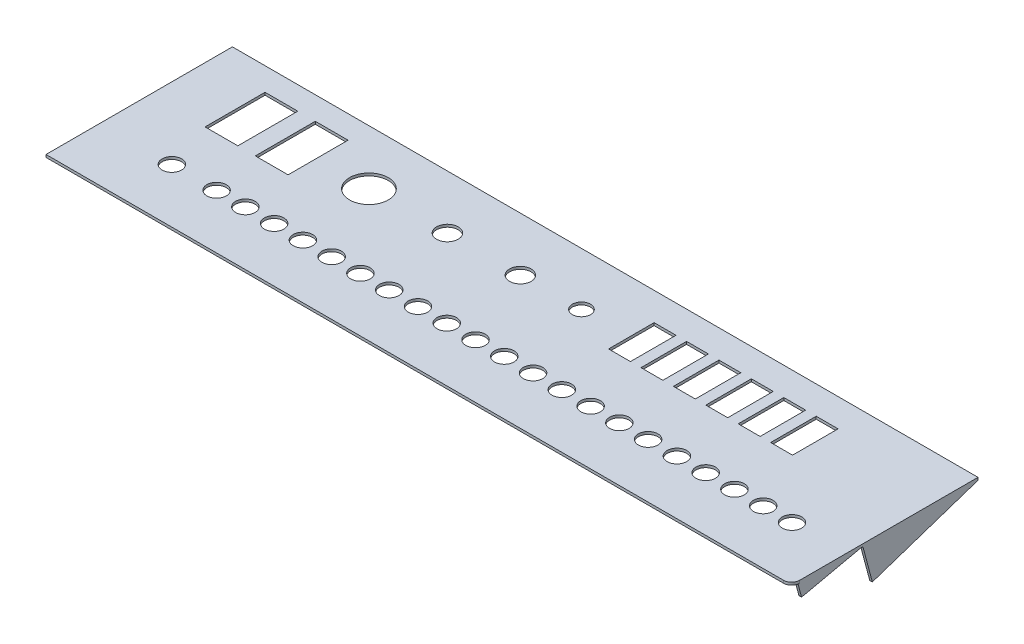
SolidWorks part; units mm, degrees
ref_plane "Front Plane" through (0, 0, 0) normal (0, 0, 1) x (1, 0, 0)
ref_plane "Top Plane" through (0, 0, 0) normal (0, 1, 0) x (1, 0, 0)
ref_plane "Right Plane" through (0, 0, 0) normal (1, 0, 0) x (0, 0, -1)
sketch "Boceto" plane through (0, 0, 0) normal (0, 1, 0) x (1, 0, 0)
  line L0 (-59.1, 30.6902) -> (-173.0029, 30.6902) construction
  line L5 (-59.1, -51.6098) -> (395.9, -51.6098) construction
  line L6 (-59.1, -51.6098) -> (-59.1, 63.3902) construction
  line L7 (-59.1, 63.3902) -> (395.9, 63.3902) construction
  line L8 (395.9, -51.6098) -> (395.9, 63.3902) construction
  line L9 (-28.6, 48.9902) -> (-8.6, 48.9902) construction
  line L10 (-28.6, 48.9902) -> (-28.6, 12.3902) construction
  line L11 (-28.6, 12.3902) -> (-8.6, 12.3902) construction
  line L12 (-8.6, 48.9902) -> (-8.6, 12.3902) construction
  line L13 (-28.6, 48.9902) -> (-8.6, 12.3902) construction
  line L14 (-28.6, 12.3902) -> (-8.6, 48.9902) construction
  line L15 (-59.1, -18.1098) -> (395.9, -18.1098) construction
  line L16 (2.4, 12.3902) -> (22.4, 12.3902) construction
  line L17 (2.4, 12.3902) -> (2.4, 48.9902) construction
  line L18 (2.4, 48.9902) -> (22.4, 48.9902) construction
  line L19 (22.4, 12.3902) -> (22.4, 48.9902) construction
  line L20 (2.4, 12.3902) -> (22.4, 48.9902) construction
  line L21 (2.4, 48.9902) -> (22.4, 12.3902) construction
  line L22 (174.9, 49.7902) -> (194.9, 49.7902) construction
  line L23 (174.9, 49.7902) -> (174.9, 11.7902) construction
  line L24 (174.9, 11.7902) -> (194.9, 11.7902) construction
  line L25 (194.9, 49.7902) -> (194.9, 11.7902) construction
  line L26 (174.9, 49.7902) -> (194.9, 11.7902) construction
  line L27 (174.9, 11.7902) -> (194.9, 49.7902) construction
  line L34 (211.4, 17.5561) -> (331, 17.5561) construction
  line L35 (211.4, 17.5561) -> (211.4, 46.5902) construction
  line L36 (211.4, 46.5902) -> (331, 46.5902) construction
  line L37 (331, 17.5561) -> (331, 46.5902) construction
  line L38 (211.4, 17.5561) -> (331, 46.5902) construction
  line L39 (211.4, 46.5902) -> (331, 17.5561) construction
  circle A0 centre (54.9, 29.6902) radius 11.1 construction
  circle A1 centre (102.75, 30.2402) radius 4.85 construction
  circle A2 centre (147.75, 30.2402) radius 4.85 construction
  circle A3 centre (-18.9, -18.1098) radius 6 construction
  circle A4 centre (8.7, -18.1098) radius 6 construction
  circle A5 centre (26.45, -18.1098) radius 6 construction
  circle A6 centre (44.2, -18.1098) radius 6 construction
  circle A7 centre (61.95, -18.1098) radius 6 construction
  circle A8 centre (79.7, -18.1098) radius 6 construction
  circle A9 centre (97.45, -18.1098) radius 6 construction
  circle A10 centre (115.2, -18.1098) radius 6 construction
  circle A11 centre (132.95, -18.1098) radius 6 construction
  circle A12 centre (150.7, -18.1098) radius 6 construction
  circle A13 centre (168.45, -18.1098) radius 6 construction
  circle A14 centre (186.2, -18.1098) radius 6 construction
  circle A15 centre (203.95, -18.1098) radius 6 construction
  circle A16 centre (221.7, -18.1098) radius 6 construction
  circle A17 centre (239.45, -18.1098) radius 6 construction
  circle A18 centre (257.2, -18.1098) radius 6 construction
  circle A19 centre (274.95, -18.1098) radius 6 construction
  circle A20 centre (292.7, -18.1098) radius 6 construction
  circle A21 centre (310.45, -18.1098) radius 6 construction
  circle A22 centre (328.2, -18.1098) radius 6 construction
  circle A23 centre (345.95, -18.1098) radius 6 construction
  circle A24 centre (363.7, -18.1098) radius 6 construction
  point P0 (0, 0)
  point P6 (-18.6, 30.6902)
  point P13 (12.4, 30.6902)
  point P24 (184.9, 30.7902)
  point P34 (271.2, 32.0731)
  dimension "D10" = 22.2
  dimension "D11" = 33.7
  dimension "D14" = 9.7
  dimension "D17" = 9.7
  dimension "D23" = 12
  dimension "D29" = 81.5
  dimension "D30" = 12
  dimension "D1" = 455
  dimension "D2" = 115
  dimension "D3" = 14.4
  dimension "D4" = 30.5
  dimension "D5" = 20
  dimension "D6" = 36.6
  dimension "D7" = 11
  dimension "D8" = 20
  dimension "D9" = 36.6
  dimension "D12" = 114
  dimension "D13" = 161.85
  dimension "D15" = 33.15
  dimension "D16" = 33.15
  dimension "D18" = 206.85
  dimension "D19" = 20
  dimension "D20" = 38
  dimension "D21" = 13.6
  dimension "D22" = 234
  dimension "D24" = 270.5
  dimension "D25" = 119.6
  dimension "D26" = 16.8
  dimension "D27" = 29.0341
  dimension "D28" = 40.2
  dimension "D31" = 27.6
  dimension "D32" = 21
sketch "Sketch4" plane through (0, 0, 0) normal (0, 1, 0) x (1, 0, 0)
  line L0 (-28.6, 48.9902) -> (-8.6, 12.3902) construction
  line L1 (-60.5474, 63.3902) -> (394.4526, 63.3902)
  line L3 (-60.5474, -51.6098) -> (391.9526, -51.6098)
  line L5 (-28.7093, 12.1902) -> (-8.4907, 12.1902)
  line L6 (-28.7093, 12.1902) -> (-28.7093, 49.1902)
  line L7 (-28.7093, 49.1902) -> (-8.4907, 49.1902)
  line L8 (-8.4907, 12.1902) -> (-8.4907, 49.1902)
  line L9 (-28.7093, 12.1902) -> (-8.4907, 49.1902) construction
  line L10 (-28.7093, 49.1902) -> (-8.4907, 12.1902) construction
  line L11 (-28.6, 12.3902) -> (-8.6, 48.9902) construction
  line L12 (2.4, 12.3902) -> (22.4, 48.9902) construction
  line L17 (2.2907, 12.1902) -> (2.2907, 49.1902)
  line L18 (2.2907, 12.1902) -> (22.5093, 12.1902)
  line L19 (22.5093, 12.1902) -> (22.5093, 49.1902)
  line L20 (2.2907, 49.1902) -> (22.5093, 49.1902)
  line L21 (102.75, 30.2402) -> (199.8359, 30.2402) construction
  line L22 (211.4, 32.0731) -> (331, 32.0731) construction
  line L23 (211.4, 17.5561) -> (211.4, 46.5902) construction
  line L24 (331, 17.5561) -> (331, 46.5902) construction
  line L25 (247.9, 46.1231) -> (247.9, 18.0231)
  line L26 (227.9, 46.1231) -> (214.4, 46.1231)
  line L27 (227.9, 46.1231) -> (227.9, 18.0231)
  line L28 (227.9, 18.0231) -> (214.4, 18.0231)
  line L29 (214.4, 46.1231) -> (214.4, 18.0231)
  line L30 (227.9, 46.1231) -> (214.4, 18.0231) construction
  line L31 (227.9, 18.0231) -> (214.4, 46.1231) construction
  line L32 (247.9, 46.1231) -> (234.4, 46.1231)
  line L33 (234.4, 46.1231) -> (234.4, 18.0231)
  line L34 (247.9, 18.0231) -> (234.4, 18.0231)
  line L35 (267.9, 46.1231) -> (267.9, 18.0231)
  line L36 (267.9, 46.1231) -> (254.4, 46.1231)
  line L37 (254.4, 46.1231) -> (254.4, 18.0231)
  line L38 (267.9, 18.0231) -> (254.4, 18.0231)
  line L39 (287.9, 46.1231) -> (287.9, 18.0231)
  line L40 (287.9, 46.1231) -> (274.4, 46.1231)
  line L41 (274.4, 46.1231) -> (274.4, 18.0231)
  line L42 (287.9, 18.0231) -> (274.4, 18.0231)
  line L43 (307.9, 46.1231) -> (307.9, 18.0231)
  line L44 (307.9, 46.1231) -> (294.4, 46.1231)
  line L45 (294.4, 46.1231) -> (294.4, 18.0231)
  line L46 (307.9, 18.0231) -> (294.4, 18.0231)
  line L47 (327.9, 46.1231) -> (327.9, 18.0231)
  line L48 (327.9, 46.1231) -> (314.4, 46.1231)
  line L49 (314.4, 46.1231) -> (314.4, 18.0231)
  line L50 (327.9, 18.0231) -> (314.4, 18.0231)
  line L52 (-60.5474, 63.3902) -> (-63.0474, 63.3902)
  line L54 (-60.5474, -51.6098) -> (-63.0474, -51.6098)
  line L55 (-63.0474, 63.3902) -> (-63.0474, -51.6098)
  line L58 (394.4526, 63.3902) -> (396.9526, 63.3902)
  line L59 (396.9526, -46.6098) -> (396.9526, 63.3902)
  circle A0 centre (54.9, 29.6902) radius 11.95
  circle A1 centre (102.75, 30.2402) radius 6.65
  circle A4 centre (147.75, 30.2402) radius 6.65
  circle A6 centre (184.9, 30.7902) radius 5.6
  circle A7 centre (-18.9, -18.1098) radius 6
  circle A8 centre (8.7, -18.1098) radius 6
  circle A9 centre (26.45, -18.1098) radius 6
  circle A10 centre (44.2, -18.1098) radius 6
  circle A11 centre (61.95, -18.1098) radius 6
  circle A12 centre (79.7, -18.1098) radius 6
  circle A13 centre (97.45, -18.1098) radius 6
  circle A14 centre (115.2, -18.1098) radius 6
  circle A15 centre (132.95, -18.1098) radius 6
  circle A16 centre (150.7, -18.1098) radius 6
  circle A17 centre (168.45, -18.1098) radius 6
  circle A18 centre (186.2, -18.1098) radius 6
  circle A19 centre (203.95, -18.1098) radius 6
  circle A20 centre (221.7, -18.1098) radius 6
  circle A21 centre (239.45, -18.1098) radius 6
  circle A22 centre (257.2, -18.1098) radius 6
  circle A23 centre (274.95, -18.1098) radius 6
  circle A24 centre (292.7, -18.1098) radius 6
  circle A25 centre (310.45, -18.1098) radius 6
  circle A26 centre (328.2, -18.1098) radius 6
  circle A27 centre (345.95, -18.1098) radius 6
  circle A28 centre (363.7, -18.1098) radius 6
  arc A29 (396.9526, -46.6098) -> (391.9526, -51.6098) centre (391.9526, -46.6098) cw
  point P6 (-18.6, 30.6902)
  point P15 (12.4, 30.6902)
  point P40 (221.15, 32.0731)
  dimension "D3" = 23.9
  dimension "D4" = 13.3
  dimension "D5" = 2
  dimension "D6" = 11.2
  dimension "D11" = 12
  dimension "D13" = 5
  dimension "D1" = 37
  dimension "D2" = 2
  dimension "D7" = 13.5
  dimension "D8" = 28.1
  dimension "D9" = 3
  dimension "D14" = 2.5
  dimension "D15" = 2.5
  dimension "D10" = 6
  dimension "D12" = 21
extrude "Boss-Extrude1" add sketch "Sketch4" along normal blind 1.6
sketch "Sketch5" plane through (396.9526, 0, 0) normal (1, 0, 0) x (0, 0, -1)
  line L0 (63.3902, 0) -> (-7.6098, 0)
  line L1 (-46.6098, 0) -> (63.3902, 0) construction
  line L2 (-7.6098, 0) -> (-1.7864, -21.7333)
  line L3 (-1.7864, -21.7333) -> (63.3902, 0)
  line L4 (-9.1098, 0) -> (-47.6098, 0)
  line L5 (-47.6098, 0) -> (-45.4662, -8)
  line L6 (-45.4662, -8) -> (-9.1098, 0)
  point P8 (0, 0)
  point P9 (0, 0)
  dimension "D1" = 71
  dimension "D2" = 22.5
  dimension "D3" = 75
  dimension "D4" = 1.5
  dimension "D5" = 8
  dimension "D6" = 75
  dimension "D7" = 38.5
extrude "Boss-Extrude2" add sketch "Sketch5" against normal blind 1.6
